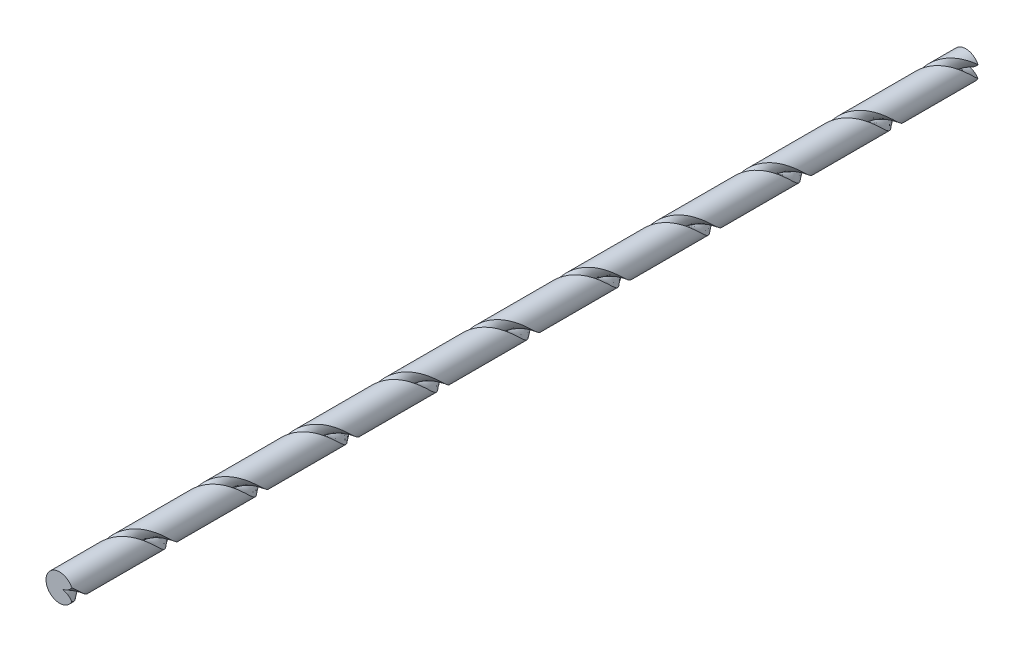
SolidWorks part; units mm, degrees
ref_plane "Alzado" through (0, 0, 0) normal (0, 0, 1) x (1, 0, 0)
ref_plane "Planta" through (0, 0, 0) normal (0, 1, 0) x (1, 0, 0)
ref_plane "Vista lateral" through (0, 0, 0) normal (1, 0, 0) x (0, 0, -1)
sketch "Croquis1" plane through (0, 0, 0) normal (0, 0, 1) x (1, 0, 0)
  circle A0 centre (0, 0) radius 3
  dimension "D1" = 6
extrude "Saliente-Extruir1" add sketch "Croquis1" along normal blind 200
sketch "Croquis2" plane through (0, 0, 200) normal (0, 0, 1) x (1, 0, 0)
  circle A1 centre (0, 0) radius 3
  circle A2 centre (0, 0) radius 3
  dimension "D1" = 0
curve "Hélice/Espiral1" pitch 20 height 1200 turns 60
sketch "Croquis4" plane through (0, 0, 0) normal (0, 1, 0) x (1, 0, 0)
  line L4 (3, -200) -> (3, -198.5566)
  line L5 (3, -200) -> (3, 0) construction
  line L6 (3, -198.5566) -> (0.5, -200)
  line L7 (-3, -200) -> (3, -200) construction
  line L8 (0.5, -200) -> (3, -201.4434)
  line L9 (3, -201.4434) -> (3, -200)
  dimension "D1" = 60
  dimension "D2" = 60
  dimension "D3" = 2.5
sweep "Cortar-Barrer2" cut profiles "Croquis4" path "Hélice/Espiral1"
